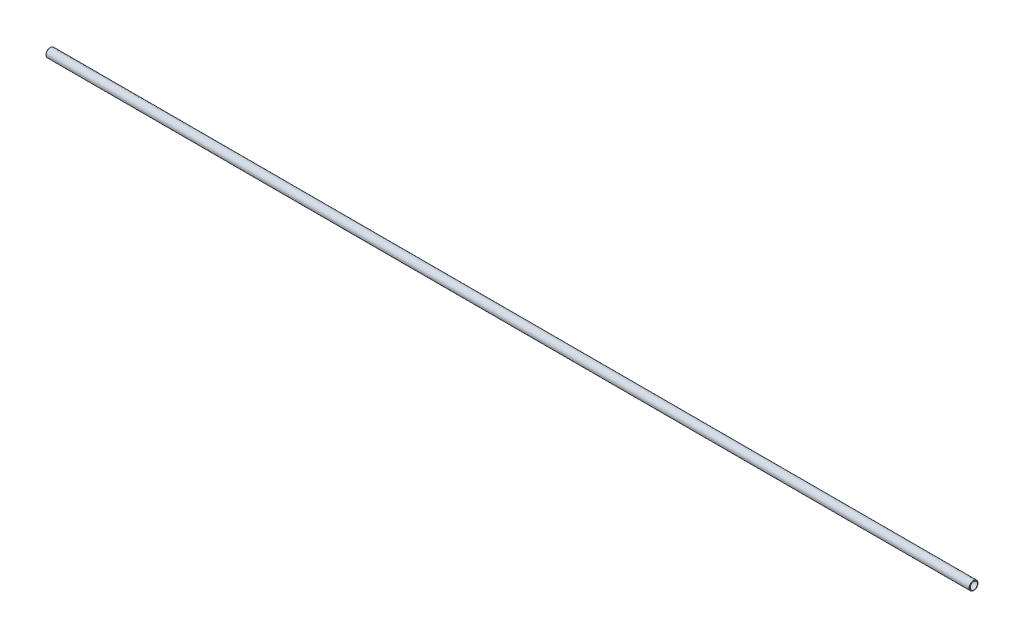
SolidWorks part; units mm, degrees
material "AISI 304"
ref_plane "Front Plane" through (0, 0, 0) normal (0, 0, 1) x (1, 0, 0)
ref_plane "Top Plane" through (0, 0, 0) normal (0, 1, 0) x (1, 0, 0)
ref_plane "Right Plane" through (0, 0, 0) normal (1, 0, 0) x (0, 0, -1)
ref_plane "Plane1" through (1289.558, 0, 0) normal (1, 0, 0) x (0, 0, -1)
sketch "Sketch1" plane through (0, 0, 0) normal (0, 0, 1) x (1, 0, 0)
  line L0 (-0.3964, 5.305) -> (-0.254, 5.1626)
  line L1 (-0.254, 5.1626) -> (0, 5.1626)
  line L2 (0, 5.1626) -> (0.508, 5.6706)
  line L3 (0.508, 5.6706) -> (1289.05, 5.6706)
  line L4 (1289.05, 5.6706) -> (1289.558, 5.1626)
  line L5 (1289.558, 5.1626) -> (1289.812, 5.1626)
  line L6 (1289.812, 5.1626) -> (1289.9544, 5.305)
  line L7 (1289.9544, 5.4846) -> (1289.4219, 6.0171)
  line L8 (1289.0627, 6.1659) -> (0.4953, 6.1658)
  line L9 (0.1361, 6.0171) -> (-0.3964, 5.4846)
  line L10 (1289.558, 0) -> (0, 0) construction
  arc A0 (-0.3964, 5.4846) -> (-0.3964, 5.305) centre (-0.3066, 5.3948) ccw
  arc A1 (1289.9544, 5.305) -> (1289.9544, 5.4846) centre (1289.8646, 5.3948) ccw
  arc A2 (1289.4219, 6.0171) -> (1289.0627, 6.1659) centre (1289.0627, 5.6579) ccw
  arc A3 (0.4953, 6.1658) -> (0.1361, 6.0171) centre (0.4953, 5.6578) ccw
revolve "Revolve1" add sketch "Sketch1" angle 360 about L10 reverse direction yes
ref_plane "Plane2" through (644.779, 0, 0) normal (1, 0, 0) x (0, 0, -1)
ref_plane "cp1 XY" through (644.779, 0, 0) normal (1, 0, 0) x (0, 0, -1)
ref_plane "cp1 XZ" through (0, 6.1658, 0) normal (0, -1, 0) x (-1, 0, 0)
ref_plane "cp1 YZ" through (0, 0, 0) normal (0, 0, -1) x (-1, 0, 0)
ref_axis "cp1 X" through (644.779, 6.1658, 80.9) along (0, 0, -1)
ref_axis "cp1 Y" through (644.779, -50, 0) along (0, 1, 0)
ref_axis "cp1 Z" through (80.9, 6.1658, 0) along (-1, 0, 0)
sketch3d "cp1"
  point P0 (644.779, 6.1658, 0)
ref_plane "cp2 XY" through (644.779, 0, 0) normal (1, 0, 0) x (0, 0, -1)
ref_plane "cp2 XZ" through (0, 0, 0) normal (0, -1, 0) x (-1, 0, 0)
ref_plane "cp2 YZ" through (0, 0, -6.1658) normal (0, 0, -1) x (-1, 0, 0)
ref_axis "cp2 X" through (644.779, 0, 80.9) along (0, 0, -1)
ref_axis "cp2 Y" through (644.779, -50, -6.1658) along (0, 1, 0)
ref_axis "cp2 Z" through (80.9, 0, -6.1658) along (-1, 0, 0)
sketch3d "cp2"
  point P0 (644.779, 0, -6.1658)
ref_plane "cp3 XY" through (644.779, 0, 0) normal (1, 0, 0) x (0, 0, -1)
ref_plane "cp3 XZ" through (0, -6.1658, 0) normal (0, -1, 0) x (-1, 0, 0)
ref_plane "cp3 YZ" through (0, 0, 0) normal (0, 0, -1) x (-1, 0, 0)
ref_axis "cp3 X" through (644.779, -6.1658, 80.9) along (0, 0, -1)
ref_axis "cp3 Y" through (644.779, -50, 0) along (0, 1, 0)
ref_axis "cp3 Z" through (80.9, -6.1658, 0) along (-1, 0, 0)
sketch3d "cp3"
  point P0 (644.779, -6.1658, 0)
ref_plane "cp4 XY" through (644.779, 0, 0) normal (1, 0, 0) x (0, 0, -1)
ref_plane "cp4 XZ" through (0, 0, 0) normal (0, -1, 0) x (-1, 0, 0)
ref_plane "cp4 YZ" through (0, 0, 6.1658) normal (0, 0, -1) x (-1, 0, 0)
ref_axis "cp4 X" through (644.779, 0, 80.9) along (0, 0, -1)
ref_axis "cp4 Y" through (644.779, -50, 6.1658) along (0, 1, 0)
ref_axis "cp4 Z" through (80.9, 0, 6.1658) along (-1, 0, 0)
sketch3d "cp4"
  point P0 (644.779, 0, 6.1658)
ref_plane "tube_front XY" through (0, 0, 0) normal (1, 0, 0) x (0, 0, -1)
ref_plane "tube_front XZ" through (0, 0, 0) normal (0, -1, 0) x (-1, 0, 0)
ref_plane "tube_front YZ" through (0, 0, 0) normal (0, 0, -1) x (-1, 0, 0)
ref_axis "tube_front X" through (0, 0, 80.9) along (0, 0, -1)
ref_axis "tube_front Y" through (0, -50, 0) along (0, 1, 0)
ref_axis "tube_front Z" through (80.9, 0, 0) along (-1, 0, 0)
sketch3d "tube_front"
  point P0 (0, 0, 0)
ref_plane "tube_rear XY" through (1289.558, 0, 0) normal (1, 0, 0) x (0, 0, -1)
ref_plane "tube_rear XZ" through (0, 0, 0) normal (0, -1, 0) x (-1, 0, 0)
ref_plane "tube_rear YZ" through (0, 0, 0) normal (0, 0, -1) x (-1, 0, 0)
ref_axis "tube_rear X" through (1289.558, 0, 80.9) along (0, 0, -1)
ref_axis "tube_rear Y" through (1289.558, -50, 0) along (0, 1, 0)
ref_axis "tube_rear Z" through (80.9, 0, 0) along (-1, 0, 0)
sketch3d "tube_rear"
  point P0 (1289.558, 0, 0)
